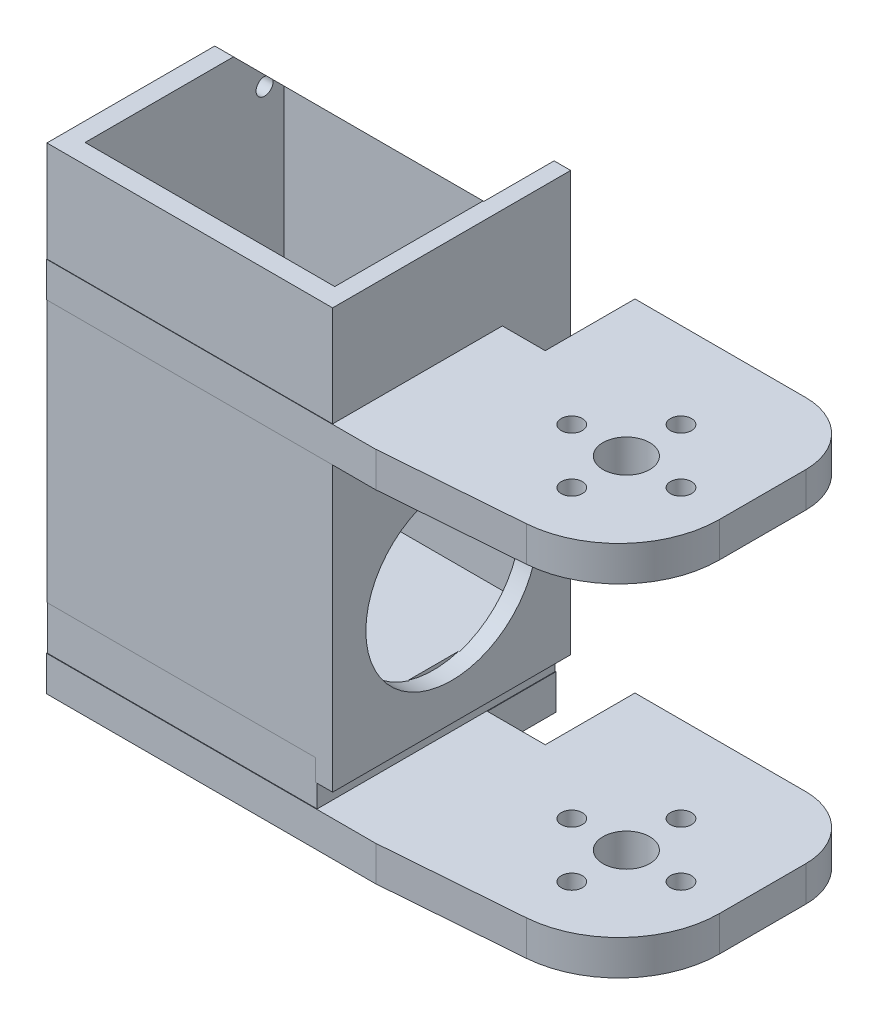
SolidWorks part; units mm, degrees
ref_plane "Front Plane" through (0, 0, 0) normal (0, 0, 1) x (1, 0, 0)
ref_plane "Top Plane" through (0, 0, 0) normal (0, 1, 0) x (1, 0, 0)
ref_plane "Right Plane" through (0, 0, 0) normal (1, 0, 0) x (0, 0, -1)
ref_plane "PY_m23_125" through (0, -23.125, 0) normal (0, 1, 0) x (1, 0, 0)
sketch "S_prism1" plane through (0, -23.125, 0) normal (0, 1, 0) x (1, 0, 0)
  line L0 (13, 10) -> (13, -1.0582)
  line L1 (1.0937, -13.9199) -> (-16.9, -15.31)
  line L2 (-16.9, -15.31) -> (-16.9, 18)
  line L3 (-16.9, 18) -> (5, 18)
  arc A0 (5, 18) -> (13, 10) centre (5.0002, 10.0002) cw
  arc A1 (13, -1.0582) -> (1.0937, -13.9199) centre (0.0999, -1.0582) cw
extrude "Boss_1" add sketch "S_prism1" along normal blind 4.5
ref_plane "PY_p18_625" through (0, 18.625, 0) normal (0, 1, 0) x (1, 0, 0)
sketch "S_cyl2" plane through (0, 18.625, 0) normal (0, 1, 0) x (1, 0, 0)
  circle A0 centre (0, 0) radius 9
  dimension "D1_S_cyl2" = 18
extrude "Boss_2" add sketch "S_cyl2" along normal blind 2
ref_plane "PY_p20_625" through (0, 20.625, 0) normal (0, 1, 0) x (1, 0, 0)
sketch "S_prism3" plane through (0, 20.625, 0) normal (0, 1, 0) x (1, 0, 0)
  line L0 (13, 10) -> (13, -1.0582)
  line L1 (1.0937, -13.9199) -> (-16.9, -15.31)
  line L2 (-16.9, -15.31) -> (-16.9, 18)
  line L3 (-16.9, 18) -> (5, 18)
  arc A0 (5, 18) -> (13, 10) centre (5.0002, 10.0002) cw
  arc A1 (13, -1.0582) -> (1.0937, -13.9199) centre (0.0999, -1.0582) cw
extrude "Boss_3" add sketch "S_prism3" along normal blind 4.5
sketch "S_prism4" plane through (0, -23.125, 0) normal (0, 1, 0) x (1, 0, 0)
  line L0 (-24.575, 6.5) -> (-16.8, 6.5)
  line L1 (-16.8, 6.5) -> (-16.8, -15.31)
  line L2 (-16.8, -15.31) -> (-24.575, -15.31)
  line L3 (-24.575, -15.31) -> (-24.575, 6.5)
extrude "Boss_4" add sketch "S_prism4" along normal blind 4.5
sketch "S_prism5" plane through (0, -23.125, 0) normal (0, 1, 0) x (1, 0, 0)
  line L0 (-59.025, -12.71) -> (-16.8, -12.71)
  line L1 (-16.8, -12.71) -> (-16.8, -15.31)
  line L2 (-16.8, -15.31) -> (-59.025, -15.31)
  line L3 (-59.025, -15.31) -> (-59.025, -12.71)
extrude "Boss_5" add sketch "S_prism5" along normal blind 4.5
sketch "S_prism6" plane through (0, -23.125, 0) normal (0, 1, 0) x (1, 0, 0)
  line L0 (-59.025, 15.31) -> (-24.325, 15.31)
  line L1 (-24.325, 15.31) -> (-24.325, -15.31)
  line L2 (-24.325, -15.31) -> (-59.025, -15.31)
  line L3 (-59.025, -15.31) -> (-59.025, 15.31)
extrude "Boss_6" add sketch "S_prism6" along normal blind 4.5
sketch "S_prism7" plane through (0, 20.625, 0) normal (0, 1, 0) x (1, 0, 0)
  line L0 (-24.575, 6.5) -> (-16.8, 6.5)
  line L1 (-16.8, 6.5) -> (-16.8, -15.31)
  line L2 (-16.8, -15.31) -> (-24.575, -15.31)
  line L3 (-24.575, -15.31) -> (-24.575, 6.5)
extrude "Boss_7" add sketch "S_prism7" along normal blind 4.5
sketch "S_prism8" plane through (0, 20.625, 0) normal (0, 1, 0) x (1, 0, 0)
  line L0 (-59.025, -12.71) -> (-16.8, -12.71)
  line L1 (-16.8, -12.71) -> (-16.8, -15.31)
  line L2 (-16.8, -15.31) -> (-59.025, -15.31)
  line L3 (-59.025, -15.31) -> (-59.025, -12.71)
extrude "Boss_8" add sketch "S_prism8" along normal blind 4.5
ref_plane "PZ_m15_260" through (0, 0, -15.26) normal (0, 0, 1) x (1, 0, 0)
sketch "S_box9" plane through (0, 0, -15.26) normal (0, 0, 1) x (1, 0, 0)
  line L0 (-59.025, -13.01) -> (-24.625, -13.01)
  line L1 (-24.625, -13.01) -> (-24.625, -10.51)
  line L2 (-24.625, -10.51) -> (-59.025, -10.51)
  line L3 (-59.025, -10.51) -> (-59.025, -13.01)
  dimension "P1" = 59.025
  dimension "P2" = 13.01
  dimension "P3" = 24.625
  dimension "P4" = 13.01
  dimension "P5" = 24.625
  dimension "P6" = 10.51
  dimension "P7" = 59.025
  dimension "P8" = 10.51
extrude "Boss_9" add sketch "S_box9" along normal blind 30.52
sketch "S_box10" plane through (0, 0, -15.26) normal (0, 0, 1) x (1, 0, 0)
  line L0 (-59.025, -13.01) -> (-24.625, -13.01)
  line L1 (-24.625, -13.01) -> (-24.625, 38.01)
  line L2 (-24.625, 38.01) -> (-59.025, 38.01)
  line L3 (-59.025, 38.01) -> (-59.025, -13.01)
  dimension "P1" = 59.025
  dimension "P2" = 13.01
  dimension "P3" = 24.625
  dimension "P4" = 13.01
  dimension "P5" = 24.625
  dimension "P6" = 38.01
  dimension "P7" = 59.025
  dimension "P8" = 38.01
extrude "Boss_10" add sketch "S_box10" along normal blind 2.5
ref_plane "PZ_p12_760" through (0, 0, 12.76) normal (0, 0, 1) x (1, 0, 0)
sketch "S_box11" plane through (0, 0, 12.76) normal (0, 0, 1) x (1, 0, 0)
  line L0 (-59.025, -13.01) -> (-24.625, -13.01)
  line L1 (-24.625, -13.01) -> (-24.625, 38.01)
  line L2 (-24.625, 38.01) -> (-59.025, 38.01)
  line L3 (-59.025, 38.01) -> (-59.025, -13.01)
  dimension "P1" = 59.025
  dimension "P2" = 13.01
  dimension "P3" = 24.625
  dimension "P4" = 13.01
  dimension "P5" = 24.625
  dimension "P6" = 38.01
  dimension "P7" = 59.025
  dimension "P8" = 38.01
extrude "Boss_11" add sketch "S_box11" along normal blind 2.5
sketch "S_box12" plane through (0, 0, -15.26) normal (0, 0, 1) x (1, 0, 0)
  line L0 (-59.025, -13.01) -> (-56.625, -13.01)
  line L1 (-56.625, -13.01) -> (-56.625, 38.01)
  line L2 (-56.625, 38.01) -> (-59.025, 38.01)
  line L3 (-59.025, 38.01) -> (-59.025, -13.01)
  dimension "P1" = 59.025
  dimension "P2" = 13.01
  dimension "P3" = 56.625
  dimension "P4" = 13.01
  dimension "P5" = 56.625
  dimension "P6" = 38.01
  dimension "P7" = 59.025
  dimension "P8" = 38.01
extrude "Boss_12" add sketch "S_box12" along normal blind 30.52
sketch "S_box13" plane through (0, 0, -15.26) normal (0, 0, 1) x (1, 0, 0)
  line L0 (-24.625, -15.76) -> (-22.4, -15.76)
  line L1 (-22.4, -15.76) -> (-22.4, 38.01)
  line L2 (-22.4, 38.01) -> (-24.625, 38.01)
  line L3 (-24.625, 38.01) -> (-24.625, -15.76)
  dimension "P1" = 24.625
  dimension "P2" = 15.76
  dimension "P3" = 22.4
  dimension "P4" = 15.76
  dimension "P5" = 22.4
  dimension "P6" = 38.01
  dimension "P7" = 24.625
  dimension "P8" = 38.01
extrude "Boss_13" add sketch "S_box13" along normal blind 30.52
ref_plane "PZ_m15_240" through (0, 0, -15.24) normal (0, 0, 1) x (1, 0, 0)
sketch "S_box14" plane through (0, 0, -15.24) normal (0, 0, 1) x (1, 0, 0)
  line L0 (-58.955, -18.725) -> (-24.395, -18.725)
  line L1 (-24.395, -18.725) -> (-24.395, -12.9)
  line L2 (-24.395, -12.9) -> (-58.955, -12.9)
  line L3 (-58.955, -12.9) -> (-58.955, -18.725)
  dimension "P1" = 58.955
  dimension "P2" = 18.725
  dimension "P3" = 24.395
  dimension "P4" = 18.725
  dimension "P5" = 24.395
  dimension "P6" = 12.9
  dimension "P7" = 58.955
  dimension "P8" = 12.9
extrude "Boss_14" add sketch "S_box14" along normal blind 30.48
ref_plane "PY_m23_225" through (0, -23.225, 0) normal (0, 1, 0) x (1, 0, 0)
sketch "S_hole15" plane through (0, -23.225, 0) normal (0, 1, 0) x (1, 0, 0)
  circle A0 centre (0, 0) radius 3
  dimension "D1_S_hole15" = 6
extrude "Hole_15" cut sketch "S_hole15" along normal blind 4.7
sketch "S_hole16" plane through (0, -23.225, 0) normal (0, 1, 0) x (1, 0, 0)
  circle A0 centre (7, 0) radius 1.35
  dimension "D1_S_hole16" = 2.7
  dimension "P2" = 7
extrude "Hole_16" cut sketch "S_hole16" along normal blind 4.7
sketch "S_hole17" plane through (0, -23.225, 0) normal (0, 1, 0) x (1, 0, 0)
  circle A0 centre (0, -7) radius 1.35
  dimension "D1_S_hole17" = 2.7
  dimension "P2" = 7
extrude "Hole_17" cut sketch "S_hole17" along normal blind 4.7
sketch "S_hole18" plane through (0, -23.225, 0) normal (0, 1, 0) x (1, 0, 0)
  circle A0 centre (-7, 0) radius 1.35
  dimension "D1_S_hole18" = 2.7
  dimension "P2" = 7
extrude "Hole_18" cut sketch "S_hole18" along normal blind 4.7
sketch "S_hole19" plane through (0, -23.225, 0) normal (0, 1, 0) x (1, 0, 0)
  circle A0 centre (0, 7) radius 1.35
  dimension "D1_S_hole19" = 2.7
  dimension "P2" = 7
extrude "Hole_19" cut sketch "S_hole19" along normal blind 4.7
ref_plane "PY_p18_525" through (0, 18.525, 0) normal (0, 1, 0) x (1, 0, 0)
sketch "S_hole20" plane through (0, 18.525, 0) normal (0, 1, 0) x (1, 0, 0)
  circle A0 centre (0, 0) radius 3
  dimension "D1_S_hole20" = 6
extrude "Hole_20" cut sketch "S_hole20" along normal blind 6.7
sketch "S_hole21" plane through (0, 18.525, 0) normal (0, 1, 0) x (1, 0, 0)
  circle A0 centre (7, 0) radius 1.35
  dimension "D1_S_hole21" = 2.7
  dimension "P2" = 7
extrude "Hole_21" cut sketch "S_hole21" along normal blind 6.7
sketch "S_hole22" plane through (0, 18.525, 0) normal (0, 1, 0) x (1, 0, 0)
  circle A0 centre (0, -7) radius 1.35
  dimension "D1_S_hole22" = 2.7
  dimension "P2" = 7
extrude "Hole_22" cut sketch "S_hole22" along normal blind 6.7
sketch "S_hole23" plane through (0, 18.525, 0) normal (0, 1, 0) x (1, 0, 0)
  circle A0 centre (-7, 0) radius 1.35
  dimension "D1_S_hole23" = 2.7
  dimension "P2" = 7
extrude "Hole_23" cut sketch "S_hole23" along normal blind 6.7
sketch "S_hole24" plane through (0, 18.525, 0) normal (0, 1, 0) x (1, 0, 0)
  circle A0 centre (0, 7) radius 1.35
  dimension "D1_S_hole24" = 2.7
  dimension "P2" = 7
extrude "Hole_24" cut sketch "S_hole24" along normal blind 6.7
ref_plane "PX_m59_125" through (-59.125, 0, 0) normal (1, 0, 0) x (0, 0, -1)
sketch "S_hole25" plane through (-59.125, 0, 0) normal (1, 0, 0) x (0, 0, -1)
  circle A0 centre (0, 0) radius 11
  dimension "D1_S_hole25" = 22
extrude "Hole_25" cut sketch "S_hole25" along normal blind 2.6
sketch "S_hole26" plane through (-59.125, 0, 0) normal (1, 0, 0) x (0, 0, -1)
  circle A0 centre (-10.25, 8.3) radius 1.1
  dimension "D1_S_hole26" = 2.2
  dimension "P2" = 10.25
  dimension "P3" = 8.3
extrude "Hole_26" cut sketch "S_hole26" along normal blind 2.6
sketch "S_hole27" plane through (-59.125, 0, 0) normal (1, 0, 0) x (0, 0, -1)
  circle A0 centre (10.25, 32.75) radius 1.1
  dimension "D1_S_hole27" = 2.2
  dimension "P2" = 10.25
  dimension "P3" = 32.75
extrude "Hole_27" cut sketch "S_hole27" along normal blind 2.6
sketch "S_hole28" plane through (-59.125, 0, 0) normal (1, 0, 0) x (0, 0, -1)
  circle A0 centre (-10.25, 32.75) radius 1.1
  dimension "D1_S_hole28" = 2.2
  dimension "P2" = 10.25
  dimension "P3" = 32.75
extrude "Hole_28" cut sketch "S_hole28" along normal blind 2.6
ref_plane "PX_m24_725" through (-24.725, 0, 0) normal (1, 0, 0) x (0, 0, -1)
sketch "S_hole29" plane through (-24.725, 0, 0) normal (1, 0, 0) x (0, 0, -1)
  circle A0 centre (0, 0) radius 11
  dimension "D1_S_hole29" = 22
extrude "Hole_29" cut sketch "S_hole29" along normal blind 2.425
sketch "S_pcut30" plane through (-59.125, 0, 0) normal (1, 0, 0) x (0, 0, -1)
  line L0 (15.86, 38.61) -> (15.86, 28.41)
  line L1 (15.86, 28.41) -> (5.66, 38.61)
  line L2 (5.66, 38.61) -> (15.86, 38.61)
extrude "Cut_30" cut sketch "S_pcut30" along normal blind 34.6
equation "\"plate_t\" = 3"
equation "\"clearance\" = 0.4"
